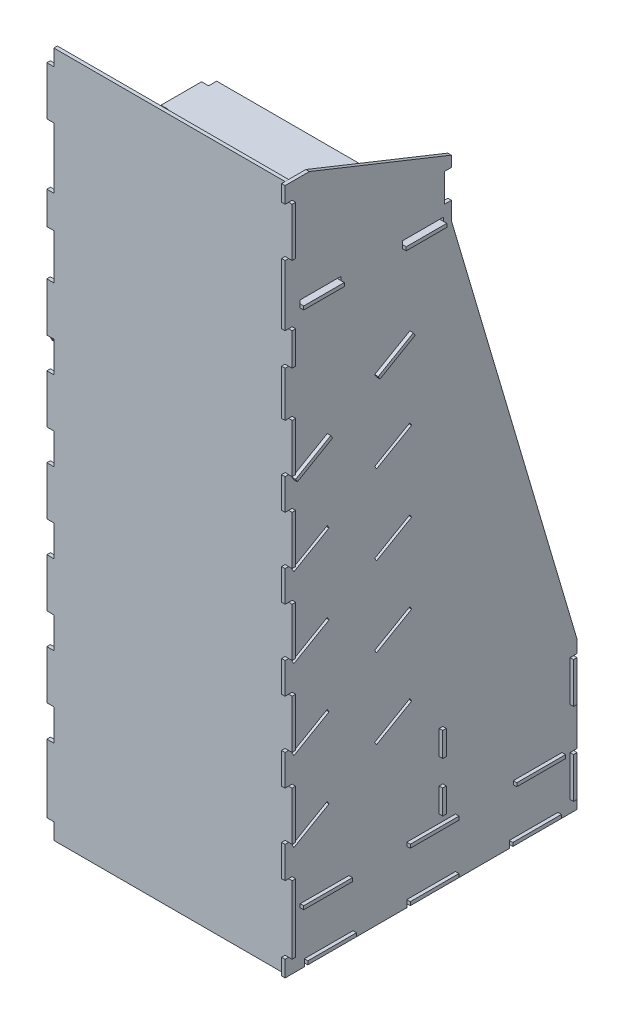
SolidWorks part; units mm, degrees
note: The reader was unsure of these and kept them because the rebuilt part matched: shared geometry of "Croquis3<3>", "Croquis3<4>", "Croquis3<5>", "Croquis3<6>", "Croquis3<7>", "Croquis3<8>".
other "BT-23-P-0104"
other "BT-23-P-0103"
other "BT-23-P-0102 "
other "BT-23-P-0101"
other "BT-23-P-0107"
other "BT-23-P-0106"
other "BT-23-P-0105" parameters "D1"=5.5, "D2"=14.633, "D3"=165.1, "D4"=166.878, "D5"=5.5865, "D6"=6.4791, "D8"=66.675, "D9"=435.2, "D10"=435.2, "D11"=435.2, "D7"=5, "D12"=5.5, "D13"=68.22, "D15"=5.5, "D16"=39.2719, "D17"=5.5, "D18"=11, "D19"=15.1654, "D20"=74.7992, "D22"=11, "D23"=11, "D24"=52.0058, "D25"=11, "D14"=3, "D21"=5
ref_plane "Alzado" through (0, 0, 0) normal (0, 0, 1) x (1, 0, 0)
ref_plane "Planta" through (0, 0, 0) normal (0, 1, 0) x (1, 0, 0)
ref_plane "Vista lateral" through (0, 0, 0) normal (1, 0, 0) x (0, 0, -1)
ref_plane "Plano1" through (-180.975, 0, 0) normal (1, 0, 0) x (0, 0, -1)
sketch "Croquis1" plane through (0, 0, 0) normal (1, 0, 0) x (0, 0, -1)
  line L0 (12.7, 251.0301) -> (50.8, 185.039)
  line L1 (12.7, 251.0301) -> (157.2206, 334.4691)
  line L2 (50.8, 185.039) -> (195.3206, 268.478)
  line L3 (157.2206, 334.4691) -> (195.3206, 268.478)
  line L4 (0, 0) -> (0, 896.5688)
  line L25 (12.7, 375.6801) -> (50.8, 309.6889)
  line L46 (12.7, 375.6801) -> (157.2206, 459.1191)
  line L47 (157.2206, 459.1191) -> (195.3206, 393.1279)
  line L48 (50.8, 309.6889) -> (195.3206, 393.1279)
  line L49 (12.7, 500.33) -> (50.8, 434.3388)
  line L50 (12.7, 500.33) -> (157.2206, 583.769)
  line L51 (157.2206, 583.769) -> (195.3206, 517.7778)
  line L52 (50.8, 434.3388) -> (195.3206, 517.7778)
  line L53 (12.7, 624.9799) -> (50.8, 558.9888)
  line L54 (12.7, 624.9799) -> (157.2206, 708.4189)
  line L55 (157.2206, 708.4189) -> (195.3206, 642.4278)
  line L56 (50.8, 558.9888) -> (195.3206, 642.4278)
  line L57 (12.7, 749.6298) -> (50.8, 683.6387)
  line L58 (12.7, 749.6298) -> (157.2206, 833.0688)
  line L59 (157.2206, 833.0688) -> (195.3206, 767.0777)
  line L60 (50.8, 683.6387) -> (195.3206, 767.0777)
  line L65 (457.2, 0) -> (457.2, 217.678)
  line L66 (263.398, 76.2) -> (444.5, 76.2)
  line L67 (263.398, 76.2) -> (263.398, 243.078)
  line L68 (263.398, 243.078) -> (444.5, 243.078)
  line L69 (444.5, 76.2) -> (444.5, 243.078)
  line L74 (12.7, 0) -> (215.9, 0) construction
  line L75 (12.7, 0) -> (12.7, 66.675) construction
  line L76 (12.7, 66.675) -> (215.9, 66.675) construction
  line L77 (215.9, 0) -> (215.9, 66.675) construction
  line L78 (12.7, 142.875) -> (215.9, 142.875) construction
  line L79 (12.7, 142.875) -> (12.7, 76.2) construction
  line L80 (12.7, 76.2) -> (215.9, 76.2) construction
  line L81 (215.9, 142.875) -> (215.9, 76.2) construction
  line L82 (241.3, 0) -> (444.5, 0) construction
  line L83 (241.3, 0) -> (241.3, 66.675) construction
  line L84 (241.3, 66.675) -> (444.5, 66.675) construction
  line L85 (444.5, 0) -> (444.5, 66.675) construction
  line L86 (157.2206, 833.0688) -> (247.65, 885.2783) construction
  line L87 (12.7, 1061.6688) -> (88.9, 1061.6688) construction
  line L88 (12.7, 1061.6688) -> (12.7, 896.5688) construction
  line L89 (12.7, 896.5688) -> (88.9, 896.5688) construction
  line L90 (88.9, 1061.6688) -> (88.9, 896.5688) construction
  line L91 (171.45, 896.5688) -> (247.65, 896.5688)
  line L92 (171.45, 896.5688) -> (171.45, 1063.4468)
  line L93 (171.45, 1063.4468) -> (247.65, 1063.4468)
  line L94 (247.65, 896.5688) -> (247.65, 1063.4468)
  point P23 (247.65, 885.0264)
  dimension "D1" = 76.2
  dimension "D2" = 166.878
  dimension "D3" = 30
  dimension "D5" = 31.75
  dimension "D6" = 12.7
  dimension "D7" = 181.102
  dimension "D8" = 25.4
  dimension "D9" = 25.4
  dimension "D10" = 66.675
  dimension "D11" = 12.7
  dimension "D12" = 63.5
  dimension "D13" = 203.2
  dimension "D14" = 9.525
  dimension "D15" = 12.7
  dimension "D16" = 76.2
  dimension "D17" = 165.1
  dimension "D18" = 12.7
  dimension "D19" = 82.55
  dimension "D20" = 25.4
  dimension "D4" = 5
sketch "Croquis2" plane through (0, 0, 0) normal (1, 0, 0) x (0, 0, -1)
  line L0 (0, 1061.6688) -> (38.1, 1061.6688)
  line L1 (38.1, 1061.6688) -> (260.35, 972.7688)
  line L2 (260.35, 972.7688) -> (260.35, 883.8688)
  line L3 (260.35, 883.8688) -> (457.2, 217.678)
  line L4 (457.2, 217.678) -> (457.2, -12.7)
  line L5 (457.2, -12.7) -> (0, -12.7)
  line L6 (0, -12.7) -> (0, 1061.6688)
  line L7 (0, 0) -> (0, 896.5688) construction
  line L8 (12.7, 0) -> (215.9, 0) construction
  line L9 (247.65, 896.5688) -> (247.65, 1063.4468) construction
  dimension "D1" = 12.7
  dimension "D2" = 12.7
  dimension "D3" = 88.9
  dimension "D4" = 38.1
  dimension "D5" = 12.7
extrude "BT-23-P-0101" add sketch "Croquis2" along normal blind 5.5
sketch "Croquis3" plane through (0, 0, 0) normal (-1, 0, 0) x (0, 0, 1)
  line L0 (-195.3206, 642.4278) -> (-198.0706, 637.6646)
  line L1 (-260.35, 883.8688) -> (-11, 883.8688)
  line L2 (-260.35, 883.8688) -> (-260.35, 889.3688)
  line L3 (-260.35, 889.3688) -> (-11, 889.3688)
  line L4 (-11, 883.8688) -> (-11, 889.3688)
  line L5 (-195.3206, 767.0777) -> (-198.0706, 762.3146)
  line L6 (-260.35, 889.3688) -> (-11, 889.3688)
  line L7 (-260.35, 889.3688) -> (-260.35, 894.8688)
  line L8 (-260.35, 894.8688) -> (-11, 894.8688)
  line L9 (-11, 889.3688) -> (-11, 894.8688)
  line L10 (-195.3206, 767.0777) -> (-11, 660.6602)
  line L11 (-198.0706, 762.3146) -> (-13.75, 655.897)
  line L12 (-11, 660.6602) -> (-13.75, 655.897)
  line L13 (-50.8, 683.6387) -> (-195.3206, 767.0777) construction
  line L14 (-195.3206, 642.4278) -> (-11, 536.0102)
  line L15 (0, -12.7) -> (-457.2, -12.7) construction
  line L16 (0, 1061.6688) -> (-5.5, 1061.6688)
  line L17 (0, 1061.6688) -> (0, -12.7)
  line L18 (0, -12.7) -> (-5.5, -12.7)
  line L19 (-5.5, 1061.6688) -> (-5.5, -12.7)
  line L20 (-38.1, 1061.6688) -> (0, 1061.6688) construction
  line L21 (-5.5, -12.7) -> (-11, -12.7)
  line L22 (-5.5, -12.7) -> (-5.5, 1061.6688)
  line L23 (-5.5, 1061.6688) -> (-11, 1061.6688)
  line L24 (-11, -12.7) -> (-11, 1061.6688)
  line L25 (-198.0706, 637.6646) -> (-13.75, 531.2471)
  line L26 (-11, 536.0102) -> (-13.75, 531.2471)
  line L27 (-11, 76.2) -> (-446.2, 76.2)
  line L28 (-11, 76.2) -> (-11, 70.7)
  line L29 (-11, 70.7) -> (-446.2, 70.7)
  line L30 (-446.2, 76.2) -> (-446.2, 70.7)
  line L31 (-12.7, 76.2) -> (-215.9, 76.2) construction
  line L32 (-195.3206, 517.7778) -> (-198.0706, 513.0147)
  line L33 (-457.2, 217.678) -> (-451.7, 217.678)
  line L34 (-457.2, 217.678) -> (-457.2, -12.7)
  line L35 (-457.2, -12.7) -> (-451.7, -12.7)
  line L36 (-451.7, 217.678) -> (-451.7, -12.7)
  line L37 (-451.7, 217.678) -> (-446.2, 217.678)
  line L38 (-451.7, 217.678) -> (-451.7, -12.7)
  line L39 (-451.7, -12.7) -> (-446.2, -12.7)
  line L40 (-446.2, 217.678) -> (-446.2, -12.7)
  line L41 (-260.35, 972.7688) -> (-254.85, 972.7688)
  line L42 (-260.35, 972.7688) -> (-260.35, 894.8688)
  line L43 (-260.35, 894.8688) -> (-254.85, 894.8688)
  line L44 (-254.85, 972.7688) -> (-254.85, 894.8688)
  line L45 (-254.85, 972.7688) -> (-249.35, 972.7688)
  line L46 (-254.85, 972.7688) -> (-254.85, 894.8688)
  line L47 (-254.85, 894.8688) -> (-249.35, 894.8688)
  line L48 (-249.35, 972.7688) -> (-249.35, 894.8688)
  line L49 (-195.3206, 517.7778) -> (-11, 411.3603)
  line L50 (-198.0706, 513.0147) -> (-13.75, 406.5972)
  line L51 (-11, 411.3603) -> (-13.75, 406.5972)
  line L52 (-195.3206, 393.1279) -> (-198.0706, 388.3648)
  line L53 (-195.3206, 393.1279) -> (-11, 286.7104)
  line L54 (-198.0706, 388.3648) -> (-13.75, 281.9472)
  line L55 (-11, 286.7104) -> (-13.75, 281.9472)
  line L56 (-195.3206, 268.478) -> (-198.0706, 263.7149)
  line L57 (-195.3206, 268.478) -> (-11, 162.0605)
  line L58 (-198.0706, 263.7149) -> (-13.75, 157.2973)
  line L59 (-11, 162.0605) -> (-13.75, 157.2973)
  line L60 (-50.8, 185.039) -> (-195.3206, 268.478) construction
  line L62 (-246.8, 76.2) -> (-241.3, 76.2)
  line L63 (-246.8, 76.2) -> (-246.8, 217.678)
  line L64 (-246.8, 217.678) -> (-241.3, 217.678)
  line L65 (-241.3, 76.2) -> (-241.3, 217.678)
  line L68 (-11, -12.7) -> (-446.2, -12.7)
  line L69 (-11, -12.7) -> (-11, -7.2)
  line L70 (-11, -7.2) -> (-446.2, -7.2)
  line L71 (-446.2, -12.7) -> (-446.2, -7.2)
  line L72 (-11, -7.2) -> (-446.2, -7.2)
  line L73 (-11, -7.2) -> (-11, -1.7)
  line L74 (-11, -1.7) -> (-446.2, -1.7)
  line L75 (-446.2, -7.2) -> (-446.2, -1.7)
  point P68 (0, 0)
  line M2 (0, 1061.6688) -> (-38.1, 1061.6688)
  line M4 (-260.35, 972.7688) -> (-260.35, 883.8688)
  line M7 (-457.2, -12.7) -> (0, -12.7)
  dimension "D1" = 5.5
  dimension "D2" = 5.5
  dimension "D3" = 5.5
  dimension "D4" = 5.5
  dimension "D5" = 5.5
  dimension "D6" = 5.5
  dimension "D9" = 5.5
  dimension "D10" = 5.5
  dimension "D11" = 5.5
sketch "Croquis4" plane through (0, 0, 0) normal (-1, 0, 0) x (0, 0, 1)
  line L0 (-260.35, 894.8688) -> (-11, 894.8688) construction
  line L1 (-247.65, 894.8688) -> (-184.15, 894.8688)
  line L2 (-247.65, 894.8688) -> (-247.65, 883.8688)
  line L3 (-247.65, 883.8688) -> (-184.15, 883.8688)
  line L4 (-184.15, 894.8688) -> (-184.15, 883.8688)
  line L5 (-260.35, 883.8688) -> (-11, 883.8688) construction
  line L6 (-260.35, 883.8688) -> (-260.35, 889.3688) construction
  line L7 (-135.675, 883.8688) -> (-135.675, 894.8688) construction
  line L8 (-87.2, 894.8688) -> (-87.2, 883.8688)
  line L9 (-23.7, 883.8688) -> (-87.2, 883.8688)
  line L10 (-23.7, 894.8688) -> (-23.7, 883.8688)
  line L11 (-23.7, 894.8688) -> (-87.2, 894.8688)
  line L12 (-195.3206, 767.0777) -> (-198.0706, 762.3146)
  line L13 (-195.3206, 767.0777) -> (-140.328, 735.3277)
  line L14 (-198.0706, 762.3146) -> (-143.078, 730.5646)
  line L15 (-140.328, 735.3277) -> (-143.078, 730.5646)
  line L16 (-105.9103, 709.1058) -> (-103.1603, 713.8689) construction
  line L17 (-198.0706, 762.3146) -> (-13.75, 655.897) construction
  line L18 (-195.3206, 767.0777) -> (-11, 660.6602) construction
  line L19 (-65.9926, 692.4102) -> (-68.7426, 687.647)
  line L20 (-13.75, 655.897) -> (-68.7426, 687.647)
  line L21 (-11, 660.6602) -> (-65.9926, 692.4102)
  line L22 (-11, 660.6602) -> (-13.75, 655.897)
  line L23 (-195.3206, 642.4278) -> (-198.0706, 637.6646)
  line L24 (-195.3206, 642.4278) -> (-140.328, 610.6778)
  line L25 (-198.0706, 637.6646) -> (-143.078, 605.9146)
  line L26 (-140.328, 610.6778) -> (-143.078, 605.9146)
  line L27 (-65.9926, 567.7602) -> (-68.7426, 562.9971)
  line L28 (-13.75, 531.2471) -> (-68.7426, 562.9971)
  line L29 (-11, 536.0102) -> (-65.9926, 567.7602)
  line L30 (-11, 536.0102) -> (-13.75, 531.2471)
  line L31 (-105.9103, 584.4559) -> (-103.1603, 589.219) construction
  line L32 (-195.3206, 517.7778) -> (-198.0706, 513.0147)
  line L33 (-195.3206, 517.7778) -> (-140.328, 486.0278)
  line L34 (-198.0706, 513.0147) -> (-143.078, 481.2647)
  line L35 (-140.328, 486.0278) -> (-143.078, 481.2647)
  line L36 (-65.9926, 443.1103) -> (-68.7426, 438.3472)
  line L37 (-13.75, 406.5972) -> (-68.7426, 438.3472)
  line L38 (-11, 411.3603) -> (-65.9926, 443.1103)
  line L39 (-11, 411.3603) -> (-13.75, 406.5972)
  line L40 (-105.9103, 459.8059) -> (-103.1603, 464.5691) construction
  line L41 (-195.3206, 393.1279) -> (-198.0706, 388.3648)
  line L42 (-195.3206, 393.1279) -> (-140.328, 361.3779)
  line L43 (-198.0706, 388.3648) -> (-143.078, 356.6148)
  line L44 (-140.328, 361.3779) -> (-143.078, 356.6148)
  line L45 (-65.9926, 318.4604) -> (-68.7426, 313.6972)
  line L46 (-13.75, 281.9472) -> (-68.7426, 313.6972)
  line L47 (-11, 286.7104) -> (-65.9926, 318.4604)
  line L48 (-11, 286.7104) -> (-13.75, 281.9472)
  line L49 (-105.9103, 335.156) -> (-103.1603, 339.9192) construction
  line L50 (-195.3206, 268.478) -> (-198.0706, 263.7149)
  line L51 (-195.3206, 268.478) -> (-140.328, 236.728)
  line L52 (-198.0706, 263.7149) -> (-143.078, 231.9649)
  line L53 (-140.328, 236.728) -> (-143.078, 231.9649)
  line L54 (-65.9926, 193.8105) -> (-68.7426, 189.0473)
  line L55 (-13.75, 157.2973) -> (-68.7426, 189.0473)
  line L56 (-11, 162.0605) -> (-65.9926, 193.8105)
  line L57 (-11, 162.0605) -> (-13.75, 157.2973)
  line L58 (-105.9103, 210.5061) -> (-103.1603, 215.2692) construction
  line L59 (-260.35, 972.7688) -> (-260.35, 894.8688) construction
  line L60 (-260.35, 956.0438) -> (-249.35, 956.0438)
  line L61 (-260.35, 956.0438) -> (-260.35, 911.5938)
  line L62 (-260.35, 911.5938) -> (-249.35, 911.5938)
  line L63 (-249.35, 956.0438) -> (-249.35, 911.5938)
  line L64 (-249.35, 972.7688) -> (-249.35, 894.8688) construction
  line L65 (0, 0) -> (0, 896.5688) construction
  line L66 (-260.35, 933.8188) -> (-249.35, 933.8188) construction
  line L67 (-457.2, 0) -> (-457.2, 217.678) construction
  line L68 (-457.2, 198.628) -> (-446.2, 198.628)
  line L69 (-457.2, 198.628) -> (-457.2, 135.128)
  line L70 (-457.2, 135.128) -> (-446.2, 135.128)
  line L71 (-446.2, 198.628) -> (-446.2, 135.128)
  line L72 (-446.2, 217.678) -> (-446.2, -12.7) construction
  line L73 (-457.2, 217.678) -> (-451.7, 217.678) construction
  line L74 (-451.7, 102.489) -> (-446.2, 102.489) construction
  line L79 (-446.2, 6.35) -> (-446.2, 69.85)
  line L80 (-457.2, 69.85) -> (-446.2, 69.85)
  line L81 (-457.2, 6.35) -> (-457.2, 69.85)
  line L82 (-457.2, 6.35) -> (-446.2, 6.35)
  line L83 (-11, 743.245) -> (0, 743.245)
  line L84 (-11, 743.245) -> (-11, 667.045)
  line L85 (-451.7, 217.678) -> (-451.7, -12.7) construction
  line L86 (-11, -1.7) -> (-446.2, -1.7) construction
  line L87 (-427.15, -1.7) -> (-350.95, -1.7)
  line L88 (-427.15, -1.7) -> (-427.15, -12.7)
  line L89 (-427.15, -12.7) -> (-350.95, -12.7)
  line L90 (-350.95, -1.7) -> (-350.95, -12.7)
  line L91 (-11, -12.7) -> (-446.2, -12.7) construction
  line L92 (-266.7, -1.7) -> (-266.7, -12.7)
  line L93 (-266.7, -1.7) -> (-190.5, -1.7)
  line L94 (-190.5, -1.7) -> (-190.5, -12.7)
  line L95 (-266.7, -12.7) -> (-190.5, -12.7)
  line L96 (-106.25, -1.7) -> (-106.25, -12.7)
  line L97 (-106.25, -1.7) -> (-30.05, -1.7)
  line L98 (-30.05, -1.7) -> (-30.05, -12.7)
  line L99 (-106.25, -12.7) -> (-30.05, -12.7)
  line L100 (-11, -12.7) -> (-11, 1061.6688) construction
  line L101 (-263.398, 76.2) -> (-444.5, 76.2) construction
  line L102 (-433.5, 76.2) -> (-357.3, 76.2)
  line L103 (-433.5, 76.2) -> (-433.5, 70.7)
  line L104 (-433.5, 70.7) -> (-357.3, 70.7)
  line L105 (-357.3, 76.2) -> (-357.3, 70.7)
  line L106 (-11, 70.7) -> (-446.2, 70.7) construction
  line L107 (-446.2, 76.2) -> (-446.2, 70.7) construction
  line L108 (-266.7, 76.2) -> (-266.7, 70.7)
  line L109 (-266.7, 76.2) -> (-190.5, 76.2)
  line L110 (-190.5, 76.2) -> (-190.5, 70.7)
  line L111 (-266.7, 70.7) -> (-190.5, 70.7)
  line L112 (-99.9, 76.2) -> (-99.9, 70.7)
  line L113 (-99.9, 76.2) -> (-23.7, 76.2)
  line L114 (-23.7, 76.2) -> (-23.7, 70.7)
  line L115 (-99.9, 70.7) -> (-23.7, 70.7)
  line L116 (-246.8, 76.2) -> (-246.8, 217.678) construction
  line L117 (-246.8, 204.978) -> (-241.3, 204.978)
  line L118 (-246.8, 204.978) -> (-246.8, 166.878)
  line L119 (-246.8, 166.878) -> (-241.3, 166.878)
  line L120 (-241.3, 204.978) -> (-241.3, 166.878)
  line L121 (-241.3, 76.2) -> (-241.3, 217.678) construction
  line L122 (-246.8, 217.678) -> (-241.3, 217.678) construction
  line L123 (-246.8, 146.939) -> (-241.3, 146.939) construction
  line L124 (-241.3, 88.9) -> (-241.3, 127)
  line L125 (-246.8, 127) -> (-241.3, 127)
  line L126 (-246.8, 88.9) -> (-246.8, 127)
  line L127 (-246.8, 88.9) -> (-241.3, 88.9)
  line L128 (0, 1061.6688) -> (0, -12.7) construction
  line L129 (-11, 1036.2688) -> (0, 1036.2688)
  line L130 (-11, 1036.2688) -> (-11, 960.0688)
  line L131 (-11, 960.0688) -> (0, 960.0688)
  line L132 (0, 1036.2688) -> (0, 960.0688)
  line L133 (0, 1061.6688) -> (-5.5, 1061.6688) construction
  line L134 (-11, 667.045) -> (0, 667.045)
  line L135 (0, 743.245) -> (0, 667.045)
  line L136 (-11, 743.245) -> (-11, 749.6298) construction
  line L137 (-11, 667.045) -> (-11, 660.6602) construction
  line L138 (-11, 618.5951) -> (-11, 542.3951)
  line L139 (-11, 618.5951) -> (0, 618.5951)
  line L140 (0, 618.5951) -> (0, 542.3951)
  line L141 (-11, 542.3951) -> (0, 542.3951)
  line L142 (-11, 493.9451) -> (-11, 417.7451)
  line L143 (-11, 493.9451) -> (0, 493.9451)
  line L144 (0, 493.9451) -> (0, 417.7451)
  line L145 (-11, 417.7451) -> (0, 417.7451)
  line L146 (-11, 369.2952) -> (-11, 293.0952)
  line L147 (-11, 369.2952) -> (0, 369.2952)
  line L148 (0, 369.2952) -> (0, 293.0952)
  line L149 (-11, 293.0952) -> (0, 293.0952)
  line L150 (-11, 244.6453) -> (-11, 168.4453)
  line L151 (-11, 244.6453) -> (0, 244.6453)
  line L152 (0, 244.6453) -> (0, 168.4453)
  line L153 (-11, 168.4453) -> (0, 168.4453)
  line L154 (-11, 162.0605) -> (-11, 168.4453) construction
  line L155 (0, -12.7) -> (-5.5, -12.7) construction
  line L156 (-11, 119.1973) -> (0, 119.1973)
  line L157 (-11, 119.1973) -> (-11, 12.7)
  line L158 (-11, 12.7) -> (0, 12.7)
  line L159 (0, 119.1973) -> (0, 12.7)
  line L161 (-11, 864.8188) -> (0, 864.8188)
  line L162 (-11, 864.8188) -> (-11, 814.0188)
  line L163 (-11, 814.0188) -> (0, 814.0188)
  line L164 (0, 864.8188) -> (0, 814.0188)
  dimension "D1" = 12.7
  dimension "D2" = 63.5
  dimension "D3" = 63.5
  dimension "D6" = 44.45
  dimension "D5" = 19.05
  dimension "D7" = 63.5
  dimension "D8" = 76.2
  dimension "D9" = 19.05
  dimension "D11" = 19.05
  dimension "D12" = 12.7
  dimension "D13" = 76.2
  dimension "D15" = 12.7
  dimension "D16" = 38.1
  dimension "D17" = 12.7
  dimension "D18" = 25.4
  dimension "D19" = 76.2
  dimension "D20" = 76.2
  dimension "D22" = 25.4
  dimension "D23" = 38.1
  dimension "D24" = 50.8
  dimension "D25" = 19.05
  dimension "D10" = 3
extrude "Cortar-Extruir1" cut sketch "Croquis4" against normal through all
extrude "BT-23-P-0102" add sketch "Croquis3" along normal blind 180.975 separate body contours L1 L4 L3 M4
sketch "Croquis5" plane through (0, 0, 0) normal (1, 0, 0) x (0, 0, -1)
  line L0 (184.15, 883.8688) -> (184.15, 894.8688) construction
  line L1 (247.65, 883.8688) -> (184.15, 883.8688)
  line L2 (247.65, 883.8688) -> (247.65, 889.3688)
  line L3 (247.65, 889.3688) -> (184.15, 889.3688)
  line L4 (184.15, 883.8688) -> (184.15, 889.3688)
  line L5 (23.7, 883.8688) -> (23.7, 894.8688) construction
  line L6 (87.2, 883.8688) -> (23.7, 883.8688)
  line L7 (87.2, 883.8688) -> (87.2, 889.3688)
  line L8 (87.2, 889.3688) -> (23.7, 889.3688)
  line L9 (23.7, 883.8688) -> (23.7, 889.3688)
extrude "Saliente-Extruir2" add sketch "Croquis5" along normal blind 11
mirror "Simetría5" about plane through (-180.975, 0, 0) normal (1, 0, 0) of bodies 104
extrude "Saliente-Extruir3" add sketch "Croquis3<3>" along normal blind 180.975 separate body contours L12 L10 L5 L11
sketch "Croquis3<3>" plane through (0, 0, 0) normal (-1, 0, 0) x (0, 0, 1) same geometry as "Croquis3"
sketch "Croquis6" plane through (0, 0, 0) normal (1, 0, 0) x (0, 0, -1)
  line L0 (195.3206, 767.0777) -> (198.0706, 762.3146)
  line L1 (195.3206, 767.0777) -> (140.328, 735.3277)
  line L2 (198.0706, 762.3146) -> (143.078, 730.5646)
  line L3 (140.328, 735.3277) -> (143.078, 730.5646)
  line L4 (65.9926, 692.4102) -> (68.7426, 687.647)
  line L5 (65.9926, 692.4102) -> (11, 660.6602)
  line L6 (68.7426, 687.647) -> (13.75, 655.897)
  line L7 (11, 660.6602) -> (13.75, 655.897)
  point P0 (13.75, 655.897)
extrude "BT-23-P-0103" add sketch "Croquis6" along normal blind 11
mirror "Simetría7" about plane through (-180.975, 0, 0) normal (1, 0, 0) of bodies 107
extrude "BT-23-P-0104" add sketch "Croquis3<4>" along normal blind 180.975 separate body contours L27 L30 L29 L24
sketch "Croquis3<4>" plane through (0, 0, 0) normal (-1, 0, 0) x (0, 0, 1) same geometry as "Croquis3"
sketch "Croquis7" plane through (0, 0, 0) normal (1, 0, 0) x (0, 0, -1)
  line L1 (433.5, 70.7) -> (357.3, 70.7)
  line L2 (433.5, 70.7) -> (433.5, 76.2)
  line L3 (433.5, 76.2) -> (357.3, 76.2)
  line L4 (357.3, 70.7) -> (357.3, 76.2)
  line L5 (266.7, 70.7) -> (190.5, 70.7)
  line L6 (266.7, 70.7) -> (266.7, 76.2)
  line L7 (266.7, 76.2) -> (190.5, 76.2)
  line L8 (190.5, 70.7) -> (190.5, 76.2)
  line L9 (99.9, 70.7) -> (23.7, 70.7)
  line L10 (99.9, 70.7) -> (99.9, 76.2)
  line L11 (99.9, 76.2) -> (23.7, 76.2)
  line L12 (23.7, 70.7) -> (23.7, 76.2)
extrude "Saliente-Extruir6" add sketch "Croquis7" along normal blind 11
mirror "Simetría8" about plane through (-180.975, 0, 0) normal (1, 0, 0) of bodies 111
extrude "BT-23-P-0105" add sketch "Croquis3<5>" along normal blind 180.975 separate body contours L40 L37 L36 L30 M7
sketch "Croquis3<5>" plane through (0, 0, 0) normal (-1, 0, 0) x (0, 0, 1) same geometry as "Croquis3"
sketch "Croquis8" plane through (0, 0, 0) normal (1, 0, 0) x (0, 0, -1)
  line L0 (457.2, 135.128) -> (446.2, 135.128) construction
  line L1 (446.2, 198.628) -> (451.7, 198.628)
  line L2 (446.2, 198.628) -> (446.2, 135.128)
  line L3 (446.2, 135.128) -> (451.7, 135.128)
  line L4 (451.7, 198.628) -> (451.7, 135.128)
  line L5 (457.2, 6.35) -> (446.2, 6.35) construction
  line L6 (446.2, 69.85) -> (451.7, 69.85)
  line L7 (446.2, 69.85) -> (446.2, 6.35)
  line L8 (446.2, 6.35) -> (451.7, 6.35)
  line L9 (451.7, 69.85) -> (451.7, 6.35)
extrude "Saliente-Extruir8" add sketch "Croquis8" along normal blind 11
mirror "Simetría9" about plane through (-180.975, 0, 0) normal (1, 0, 0) of bodies 114
extrude "Saliente-Extruir9" add sketch "Croquis3<6>" along normal blind 180.975 separate body contours L27 L65 L64 L63
sketch "Croquis3<6>" plane through (0, 0, 0) normal (-1, 0, 0) x (0, 0, 1) same geometry as "Croquis3"
sketch "Croquis9" plane through (0, 0, 0) normal (1, 0, 0) x (0, 0, -1)
  line L1 (241.3, 204.978) -> (246.8, 204.978)
  line L2 (241.3, 204.978) -> (241.3, 166.878)
  line L3 (241.3, 166.878) -> (246.8, 166.878)
  line L4 (246.8, 204.978) -> (246.8, 166.878)
  line L5 (241.3, 127) -> (246.8, 127)
  line L6 (241.3, 127) -> (241.3, 88.9)
  line L7 (241.3, 88.9) -> (246.8, 88.9)
  line L8 (246.8, 127) -> (246.8, 88.9)
extrude "Saliente-Extruir10" add sketch "Croquis9" along normal blind 11
mirror "Simetría10" about plane through (-180.975, 0, 0) normal (1, 0, 0) of bodies 117
extrude "Saliente-Extruir11" add sketch "Croquis3<7>" along normal blind 180.975 separate body contours L24 L19 L9 L4 M7 M2
sketch "Croquis3<7>" plane through (0, 0, 0) normal (-1, 0, 0) x (0, 0, 1) same geometry as "Croquis3"
sketch "Croquis10" plane through (0, 0, 0) normal (1, 0, 0) x (0, 0, -1)
  line L0 (11, 960.0688) -> (0, 960.0688) construction
  line L1 (11, 1036.2688) -> (5.5, 1036.2688)
  line L2 (11, 1036.2688) -> (11, 960.0688)
  line L3 (11, 960.0688) -> (5.5, 960.0688)
  line L4 (5.5, 1036.2688) -> (5.5, 960.0688)
  line L5 (11, 814.0188) -> (0, 814.0188) construction
  line L6 (11, 864.8188) -> (5.5, 864.8188)
  line L7 (11, 864.8188) -> (11, 814.0188)
  line L8 (11, 814.0188) -> (5.5, 814.0188)
  line L9 (5.5, 864.8188) -> (5.5, 814.0188)
  line L10 (11, 667.045) -> (0, 667.045) construction
  line L11 (11, 743.245) -> (5.5, 743.245)
  line L12 (11, 743.245) -> (11, 667.045)
  line L13 (11, 667.045) -> (5.5, 667.045)
  line L14 (5.5, 743.245) -> (5.5, 667.045)
  line L15 (11, 542.3951) -> (0, 542.3951) construction
  line L16 (11, 618.5951) -> (5.5, 618.5951)
  line L17 (11, 618.5951) -> (11, 542.3951)
  line L18 (11, 542.3951) -> (5.5, 542.3951)
  line L19 (5.5, 618.5951) -> (5.5, 542.3951)
  line L20 (11, 417.7451) -> (0, 417.7451) construction
  line L21 (11, 493.9451) -> (5.5, 493.9451)
  line L22 (11, 493.9451) -> (11, 417.7451)
  line L23 (11, 417.7451) -> (5.5, 417.7451)
  line L24 (5.5, 493.9451) -> (5.5, 417.7451)
  line L25 (11, 293.0952) -> (0, 293.0952) construction
  line L26 (11, 369.2952) -> (5.5, 369.2952)
  line L27 (11, 369.2952) -> (11, 293.0952)
  line L28 (11, 293.0952) -> (5.5, 293.0952)
  line L29 (5.5, 369.2952) -> (5.5, 293.0952)
  line L30 (11, 168.4453) -> (0, 168.4453) construction
  line L31 (11, 244.6453) -> (5.5, 244.6453)
  line L32 (11, 244.6453) -> (11, 168.4453)
  line L33 (11, 168.4453) -> (5.5, 168.4453)
  line L34 (5.5, 244.6453) -> (5.5, 168.4453)
  line L35 (11, 12.7) -> (0, 12.7) construction
  line L36 (11, 119.1973) -> (5.5, 119.1973)
  line L37 (11, 119.1973) -> (11, 12.7)
  line L38 (11, 12.7) -> (5.5, 12.7)
  line L39 (5.5, 119.1973) -> (5.5, 12.7)
extrude "Saliente-Extruir12" add sketch "Croquis10" along normal blind 11
mirror "Simetría11" about plane through (-180.975, 0, 0) normal (1, 0, 0) of bodies 120
extrude "Saliente-Extruir13" add sketch "Croquis3<8>" along normal blind 180.975 separate body contours L24 L74 L40 L70
sketch "Croquis3<8>" plane through (0, 0, 0) normal (-1, 0, 0) x (0, 0, 1) same geometry as "Croquis3"
sketch "Croquis11" plane through (0, 0, 0) normal (1, 0, 0) x (0, 0, -1)
  line L0 (106.25, -1.7) -> (106.25, -12.7) construction
  line L1 (30.05, -1.7) -> (106.25, -1.7)
  line L2 (30.05, -1.7) -> (30.05, -7.2)
  line L3 (30.05, -7.2) -> (106.25, -7.2)
  line L4 (106.25, -1.7) -> (106.25, -7.2)
  line L5 (266.7, -1.7) -> (266.7, -12.7) construction
  line L6 (190.5, -1.7) -> (266.7, -1.7)
  line L7 (190.5, -1.7) -> (190.5, -7.2)
  line L8 (190.5, -7.2) -> (266.7, -7.2)
  line L9 (266.7, -1.7) -> (266.7, -7.2)
  line L10 (427.15, -1.7) -> (427.15, -12.7) construction
  line L11 (350.95, -1.7) -> (427.15, -1.7)
  line L12 (350.95, -1.7) -> (350.95, -7.2)
  line L13 (350.95, -7.2) -> (427.15, -7.2)
  line L14 (427.15, -1.7) -> (427.15, -7.2)
extrude "Saliente-Extruir14" add sketch "Croquis11" along normal blind 11
mirror "Simetría12" about plane through (-180.975, 0, 0) normal (1, 0, 0) of bodies 123
sketch "Croquis12" plane through (-180.975, 0, 0) normal (1, 0, 0) x (0, 0, -1)
  line L0 (198.0706, 883.8688) -> (198.0706, 270.0657)
  line L1 (247.65, 883.8688) -> (184.15, 883.8688) construction
  line L2 (195.3206, 268.478) -> (198.0706, 270.0657) construction
  line L3 (140.328, 236.728) -> (195.3206, 268.478) construction
  line L4 (198.0706, 883.8688) -> (11, 883.8688)
  line L5 (11, 883.8688) -> (11, 162.0605)
  line L6 (11, 162.0605) -> (198.0706, 270.0657)
  line L7 (11, 660.6602) -> (11, 654.3093)
  line L8 (11, 654.3093) -> (105.9103, 709.1058)
  line L9 (143.078, 730.5646) -> (68.7426, 687.647) construction
  line L10 (105.9103, 709.1058) -> (103.1603, 713.8689)
  line L11 (140.328, 735.3277) -> (65.9926, 692.4102) construction
  line L12 (103.1603, 713.8689) -> (11, 660.6602)
  line L13 (11, 618.5951) -> (11, 667.045) construction
  line L14 (105.9103, 584.4559) -> (103.1603, 589.219)
  line L15 (103.1603, 589.219) -> (11, 536.0102)
  line L16 (11, 529.6594) -> (105.9103, 584.4559)
  line L17 (105.9103, 459.8059) -> (103.1603, 464.5691)
  line L18 (103.1603, 464.5691) -> (11, 411.3603)
  line L19 (11, 405.0095) -> (105.9103, 459.8059)
  line L20 (105.9103, 335.156) -> (103.1603, 339.9192)
  line L21 (103.1603, 339.9192) -> (11, 286.7104)
  line L22 (11, 280.3595) -> (105.9103, 335.156)
  line L23 (105.9103, 210.5061) -> (103.1603, 215.2692)
  line L24 (103.1603, 215.2692) -> (11, 162.0605)
  line L25 (11, 155.7096) -> (105.9103, 210.5061)
  line L26 (11, 286.7104) -> (65.9926, 318.4604) construction
  dimension "D1" = 5
extrude "Saliente-Extruir15" add sketch "Croquis12" along normal blind 5.5 separate body contours L22 L5 L6 L0 L4 L12 L10 L8 L15 L14 L16 L18 L17 L19 L21 L20
equation "\"MDF\"= 5.5mm"
equation "\"ChinCho\"= 0.125pulgadas"
equation "\"SepaChinCho\"= 0.375pulgadas"
equation "\"D1@BT-23-P-0101\" = \"MDF\""
equation "\"D1@Croquis3\"=\"MDF\""
equation "\"AnchoInterno\" = 14.25pulgadas"
equation "\"D2@Croquis3\"=\"MDF\""
equation "\"D3@Croquis3\"=\"MDF\""
equation "\"D4@Croquis3\"=\"MDF\""
equation "\"D5@Croquis3\"=\"MDF\""
equation "\"D6@Croquis3\"=\"MDF\""
equation "\"D9@Croquis3\"=\"MDF\""
equation "\"D10@Croquis3\"=\"MDF\""
equation "\"D11@Croquis3\"=\"MDF\""
equation "\"D11@Croquis4\"=\"D9@Croquis4\""
equation "\"D15@Croquis4\"=\"D12@Croquis4\""
equation "\"D1@BT-23-P-0102\"=\"MedioAncho\""
equation "\"D1@Plano1\"=\"MedioAncho\""
equation "\"MedioAncho\"= \"AnchoInterno\" / 2"
equation "\"D1@Saliente-Extruir3\"=\"MedioAncho\""
equation "\"D1@BT-23-P-0103\" = \"MDF\" * 2"
equation "\"D1@Saliente-Extruir2\"=\"MDF\"*2"
equation "\"D1@BT-23-P-0104\" = \"MedioAncho\""
equation "\"D1@Saliente-Extruir6\"=\"MDF\"*2"
equation "\"D1@BT-23-P-0105\" = \"MedioAncho\""
equation "\"D1@Saliente-Extruir8\"=\"MDF\"*2"
equation "\"D1@Saliente-Extruir9\"=\"MedioAncho\""
equation "\"D1@Saliente-Extruir10\"=\"MDF\"*2"
equation "\"D1@Saliente-Extruir11\"=\"MedioAncho\""
equation "\"D1@Saliente-Extruir12\"=\"MDF\"*2"
equation "\"D1@Saliente-Extruir13\"=\"MedioAncho\""
equation "\"D1@Saliente-Extruir14\"=\"MDF\"*2"
equation "\"D1@Saliente-Extruir15\"=\"MDF\""
